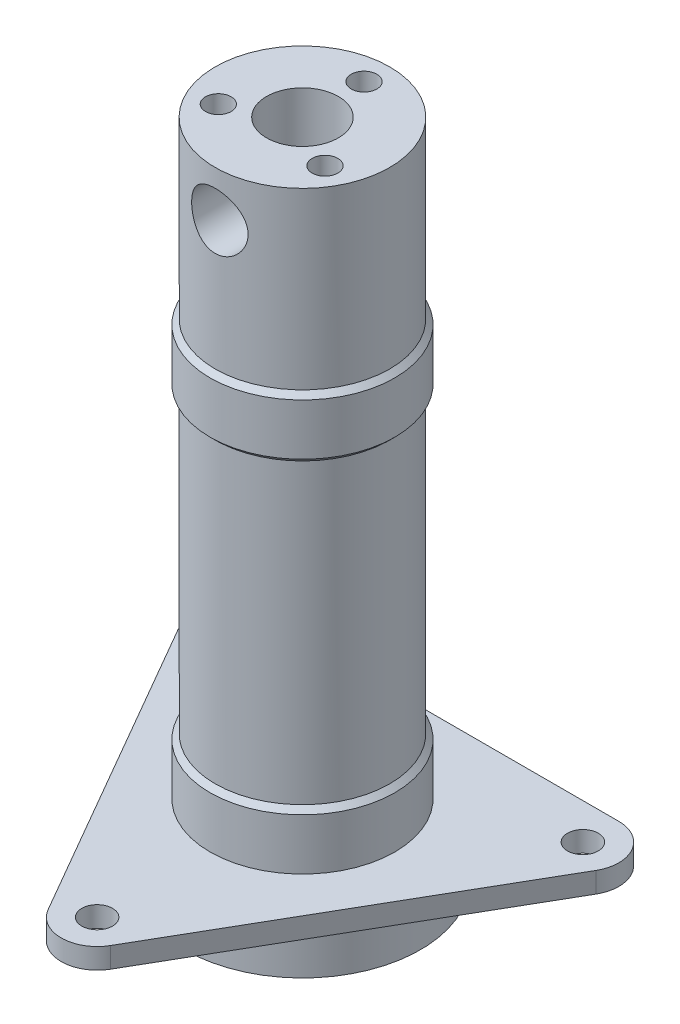
SolidWorks part; units mm, degrees
material "1060 合金"
ref_plane "前视基准面" through (0, 0, 0) normal (0, 0, 1) x (1, 0, 0)
ref_plane "上视基准面" through (0, 0, 0) normal (0, 1, 0) x (1, 0, 0)
ref_plane "右视基准面" through (0, 0, 0) normal (1, 0, 0) x (0, 0, -1)
sketch "草图2" plane through (0, 0, 0) normal (0, 0, 1) x (1, 0, 0)
  line L0 (0, 0) -> (0, 53) construction
  line L4 (9, 2) -> (9, 7)
  line L5 (8.5, 59.5) -> (3.5, 59.5)
  line L6 (3.5, 59.5) -> (3.5, 51)
  line L8 (23.5, 2) -> (23.5, 0)
  line L12 (23.5, 2) -> (9, 2)
  line L13 (6.5, 48) -> (6.5, -5)
  line L14 (11.5, 0) -> (11.5, -5)
  line L15 (11.5, -5) -> (6.5, -5)
  line L17 (11.5, 0) -> (23.5, 0)
  line L18 (8.5, 59.5) -> (8.5, 42)
  line L19 (8.5, 42) -> (9, 42)
  line L21 (6.5, 48) -> (3.5, 51)
  line L22 (9, 37) -> (9, 42)
  line L23 (9, 37) -> (8.5, 37)
  line L25 (9, 7) -> (8.5, 7)
  line L26 (8.5, 37) -> (8.5, 7)
  dimension "D1" = 13
  dimension "D2" = 2
  dimension "D3" = 23
  dimension "D4" = 18
  dimension "D5" = 23.5
  dimension "D6" = 7
  dimension "D7" = 17.5
  dimension "D8" = 5
  dimension "D9" = 5
  dimension "D10" = 17
  dimension "D11" = 40
  dimension "D12" = 5
  dimension "D13" = 135
  dimension "D14" = 8.5
revolve "旋转1" add sketch "草图2" angle 360 about L0
chamfer "倒角1" distance 0.5 angle 45 3 edges at (0, 42, -8.5) (0, 37, -8.5) (0, 7, -8.5)
chamfer "倒角2" distance 1 angle 45 1 edges at (0, 0, -11.5)
sketch "草图9" plane through (0, 0, 0) normal (0, -1, 0) x (1, 0, 0)
  line L0 (0, 0) -> (0, 20) construction
  line L1 (-3.0311, 21.75) -> (-20.3516, -8.25)
  line L2 (20.3516, -8.25) -> (3.0311, 21.75)
  line L3 (-17.3205, -13.5) -> (17.3205, -13.5)
  circle A0 centre (0, 20) radius 1.5
  circle A1 centre (17.3205, -10) radius 1.5
  circle A2 centre (-17.3205, -10) radius 1.5
  circle A3 centre (0, 0) radius 20 construction
  circle A4 centre (0, 0) radius 23.5 construction
  arc A5 (3.0311, 21.75) -> (-3.0311, 21.75) centre (0, 20) ccw
  arc A6 (17.3205, -13.5) -> (20.3516, -8.25) centre (17.3205, -10) ccw
  arc A7 (-20.3516, -8.25) -> (-17.3205, -13.5) centre (-17.3205, -10) ccw
  circle A8 centre (0, 0) radius 9 construction
  dimension "D2" = 3
  dimension "D4" = 18
  dimension "D1" = 40
  dimension "D3" = 3
extrude "切除-拉伸2" cut sketch "草图9" against normal through all flip side to cut
hole_wizard "M3 螺纹孔1" positions "草图13" profile "草图14" tap size "M3" standard "GB"
sketch "草图13" plane through (0, -5, 0) normal (0, 1, 0) x (1, 0, 0)
  circle A0 centre (0, 0) radius 9 construction
  point P0 (0, 9)
  point P10 (7.7942, -4.5)
  point P11 (-7.7942, -4.5)
  point P13 (0, 0)
  point P14 (0, 9)
  point P15 (-7.2238, -5.3682)
  point P16 (7.8043, -4.4825)
  dimension "D1" = 18
  dimension "D2" = 3
cosmetic thread "孔螺蚊线1" parameters "D1"=5, "D2"=3
cosmetic thread "孔螺蚊线2" parameters "D1"=5, "D2"=3
cosmetic thread "孔螺蚊线3" parameters "D1"=5, "D2"=3
sketch "草图14" plane through (0, -5, -9) normal (1, 0, 0) x (0, 0, -1)
  line L0 (0, 0) -> (0, 5.7511)
  line L1 (0, 5.7511) -> (1.25, 5)
  line L2 (1.25, 5) -> (1.25, 0)
  line L5 (1.25, 0) -> (0, 0)
  line L10 (0, 5.7511) -> (-1.25, 5) construction
  line L11 (0, -6.35) -> (0, 107.95) construction
  dimension "螺纹孔钻头直径" = 2.5
  dimension "螺纹孔钻头深度" = 5
  dimension "导头角度" = 118
hole_wizard "M3 螺纹孔2" positions "草图15" profile "草图16" tap size "M3" standard "GB"
sketch "草图15" plane through (0, 59.5, 0) normal (0, 1, 0) x (1, 0, 0)
  circle A0 centre (0, 0) radius 6 construction
  point P0 (0, 6)
  point P14 (5.1962, -3)
  point P15 (-5.1962, -3)
  point P17 (-4.5419, -3.9205)
  point P18 (5.1766, -3.0336)
  dimension "D1" = 12
  dimension "D2" = 3
cosmetic thread "孔螺蚊线4" parameters "D1"=6, "D2"=3
cosmetic thread "孔螺蚊线5" parameters "D1"=6, "D2"=3
cosmetic thread "孔螺蚊线6" parameters "D1"=6, "D2"=3
sketch "草图16" plane through (0, 59.5, -6) normal (1, 0, 0) x (0, 0, 1)
  line L0 (0, 0) -> (0, 7.2511)
  line L1 (0, 7.2511) -> (1.25, 6.5)
  line L2 (1.25, 6.5) -> (1.25, 0)
  line L5 (1.25, 0) -> (0, 0)
  line L10 (0, 7.2511) -> (-1.25, 6.5) construction
  line L11 (0, -6.35) -> (0, 107.95) construction
  dimension "螺纹孔钻头直径" = 2.5
  dimension "螺纹孔钻头深度" = 6.5
  dimension "导头角度" = 118
sketch "草图11" plane through (0, 0, 0) normal (0, 0, 1) x (1, 0, 0)
  line L0 (0, 0) -> (0, 59.5) construction
  line L5 (3.5, 59.5) -> (-3.5, 59.5) construction
  line L6 (8.5, 59.5) -> (-8.5, 59.5) construction
  circle A2 centre (0, 55) radius 2.75
  point P9 (0, 55.5)
  dimension "D1" = 5.5
  dimension "D2" = 4.5
extrude "切除-拉伸4" cut sketch "草图11" along normal through all
